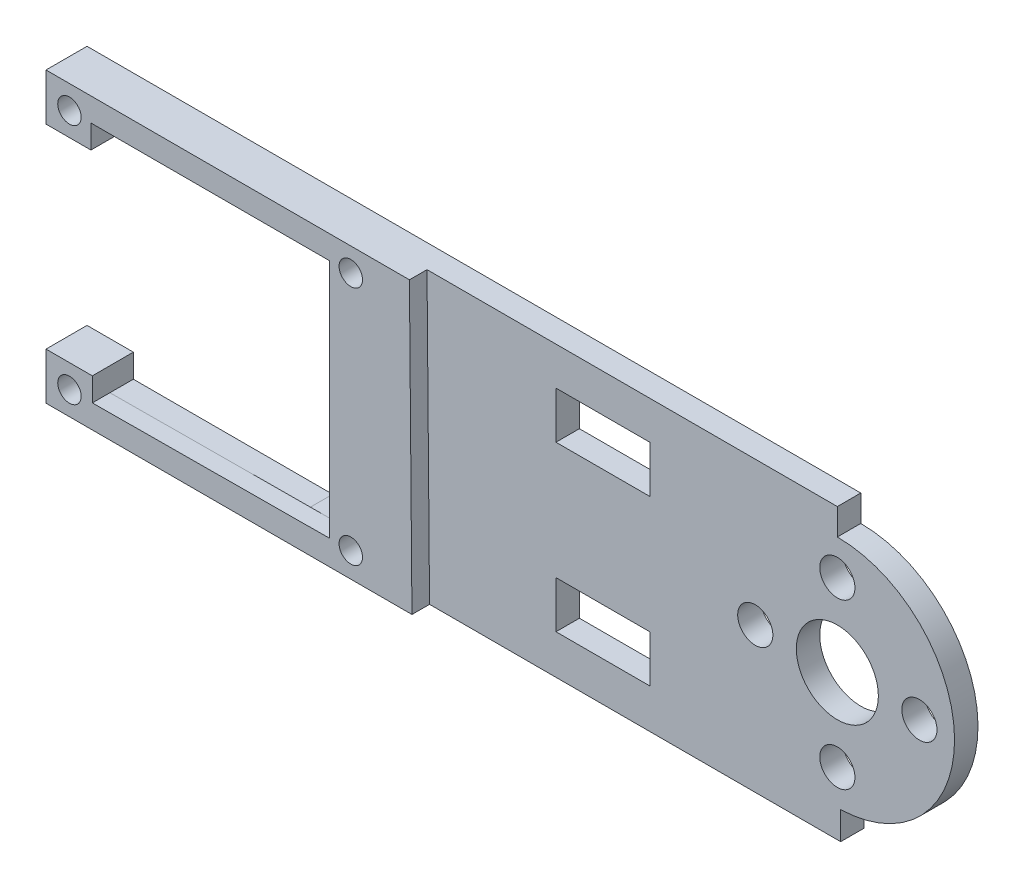
SolidWorks part; units mm, degrees
ref_plane "Front Plane" through (0, 0, 0) normal (0, 0, 1) x (1, 0, 0)
ref_plane "Top Plane" through (0, 0, 0) normal (0, 1, 0) x (1, 0, 0)
ref_plane "Right Plane" through (0, 0, 0) normal (1, 0, 0) x (0, 0, -1)
sketch "Sketch1" plane through (0, 0, 0) normal (0, 0, 1) x (1, 0, 0)
  line L0 (-5.1665, 12.25) -> (-17.1665, 12.25)
  line L1 (-5.1665, 12.25) -> (5, 12.25)
  line L3 (-5.0482, -12.3681) -> (5.2163, -12.3681)
  line L5 (-5.1665, 12.25) -> (5.2163, -12.3681) construction
  line L6 (-5.0482, -12.3681) -> (5, 12.25) construction
  line L8 (-17.1665, 10.25) -> (-5.0482, 10.25)
  line L9 (-5.0482, -12.3681) -> (-17.0482, -12.3681)
  line L11 (-17.0482, -10.3681) -> (-5.0482, -10.3681)
  line L12 (5, 12.25) -> (40, 12.25)
  line L13 (40, 12.25) -> (40, 10)
  line L14 (40.2847, -12.3681) -> (5.2163, -12.3681)
  line L15 (-5.0482, 10.25) -> (-1.7982, 10.25)
  line L16 (40.2847, -9.9959) -> (40.2847, -12.3681)
  line L17 (16, 9) -> (24, 9)
  line L18 (16, 9) -> (16, 5)
  line L19 (16, 5) -> (24, 5)
  line L20 (24, 9) -> (24, 5)
  line L21 (16, 9) -> (24, 5) construction
  line L22 (16, 5) -> (24, 9) construction
  line L23 (16, -5) -> (24, -5)
  line L24 (16, -5) -> (16, -9)
  line L25 (16, -9) -> (24, -9)
  line L26 (24, -5) -> (24, -9)
  line L27 (16, -5) -> (24, -9) construction
  line L28 (16, -9) -> (24, -5) construction
  line L29 (-1.7982, 10.25) -> (-1.7982, -10.25)
  line L30 (-1.7982, -10.25) -> (-5.0482, -10.3681)
  line L32 (-17.0482, -10.3681) -> (-22.0482, -10.3681)
  line L33 (-25, 8.25) -> (-22.1665, 8.25)
  line L34 (-22.1665, 8.25) -> (-22.1665, 10.25)
  line L35 (-22.1665, 10.25) -> (-17.1665, 10.25)
  line L36 (-17.0482, -12.3681) -> (-24, -12.3681)
  line L37 (-22.0482, -10.3681) -> (-22.0482, -8.3681)
  line L38 (-22.0482, -8.3681) -> (-26, -8.3681)
  line L39 (-26, -8.3681) -> (-26, -12.3681)
  line L40 (-26, -12.3681) -> (-24, -12.3681)
  line L41 (-17.1665, 12.25) -> (-26, 12.25)
  line L42 (-26, 12.25) -> (-26, 8.25)
  line L43 (-26, 8.25) -> (-25, 8.25)
  circle A0 centre (0, 10.25) radius 1
  circle A1 centre (0, -10.25) radius 1
  arc A2 (40.2847, -9.9959) -> (40, 10) centre (40, 0) ccw
  circle A3 centre (40, 7) radius 1.5
  circle A4 centre (47, 0) radius 1.5
  circle A5 centre (40, -7) radius 1.5
  circle A6 centre (33, 0) radius 1.5
  circle A7 centre (40, 0) radius 3.5
  circle A8 centre (-24, 10.25) radius 1
  circle A9 centre (-24, -10.3681) radius 1
  point P4 (0, 0)
  point P22 (20, 7)
  point P35 (20, -7)
  dimension "D3" = 2
  dimension "D4" = 2
  dimension "D11" = 20
  dimension "D12" = 3
  dimension "D15" = 7
  dimension "D30" = 2
  dimension "D31" = 2
  dimension "D1" = 20.5
  dimension "D2" = 10.25
  dimension "D5" = 2
  dimension "D6" = 2
  dimension "D7" = 2
  dimension "D8" = 12
  dimension "D9" = 12
  dimension "D10" = 35
  dimension "D13" = 7
  dimension "D16" = 0
  dimension "D17" = 3.25
  dimension "D18" = 3.25
  dimension "D19" = 20
  dimension "D20" = 4
  dimension "D21" = 4
  dimension "D22" = 8
  dimension "D23" = 8
  dimension "D24" = 40
  dimension "D25" = 3.25
  dimension "D27" = 24
  dimension "D28" = 2
  dimension "D29" = 26
  dimension "D32" = 24
  dimension "D33" = 24
  dimension "D34" = 5
  dimension "D36" = 26
  dimension "D37" = 5
  dimension "D14" = 4
extrude "Boss-Extrude1" add sketch "Sketch1" along normal blind 2
sketch "Sketch5" plane through (0, 0, 2) normal (0, 0, 1) x (1, 0, 0)
  line L0 (5, 12.25) -> (5.2163, -12.3681)
  line L1 (5.2163, -12.3681) -> (-26, -12.3681)
  line L2 (-26, -12.3681) -> (-26, -8.3681)
  line L3 (-26, -8.3681) -> (-22.0482, -8.3681)
  line L4 (-22.0482, -8.3681) -> (-22.0482, -10.3681)
  line L5 (-22.0482, -10.3681) -> (-1.7982, -10.25)
  line L6 (-1.7982, -10.25) -> (-1.7982, 10.25)
  line L7 (-1.7982, 10.25) -> (-22.1665, 10.25)
  line L8 (-22.1665, 10.25) -> (-22.1665, 8.25)
  line L9 (-22.1665, 8.25) -> (-26, 8.25)
  line L10 (-26, 8.25) -> (-26, 12.25)
  line L11 (-26, 12.25) -> (5, 12.25)
extrude "Boss-Extrude2" add sketch "Sketch5" along normal blind 1.5
sketch "Sketch6" plane through (0, 0, 0) normal (0, 0, -1) x (-1, 0, 0)
  circle A0 centre (0, 10.25) radius 1
  circle A1 centre (0, -10.25) radius 1
  circle A2 centre (24, -10.3681) radius 1
  circle A3 centre (24, 10.25) radius 1
extrude "Cut-Extrude1" cut sketch "Sketch6" against normal through all
